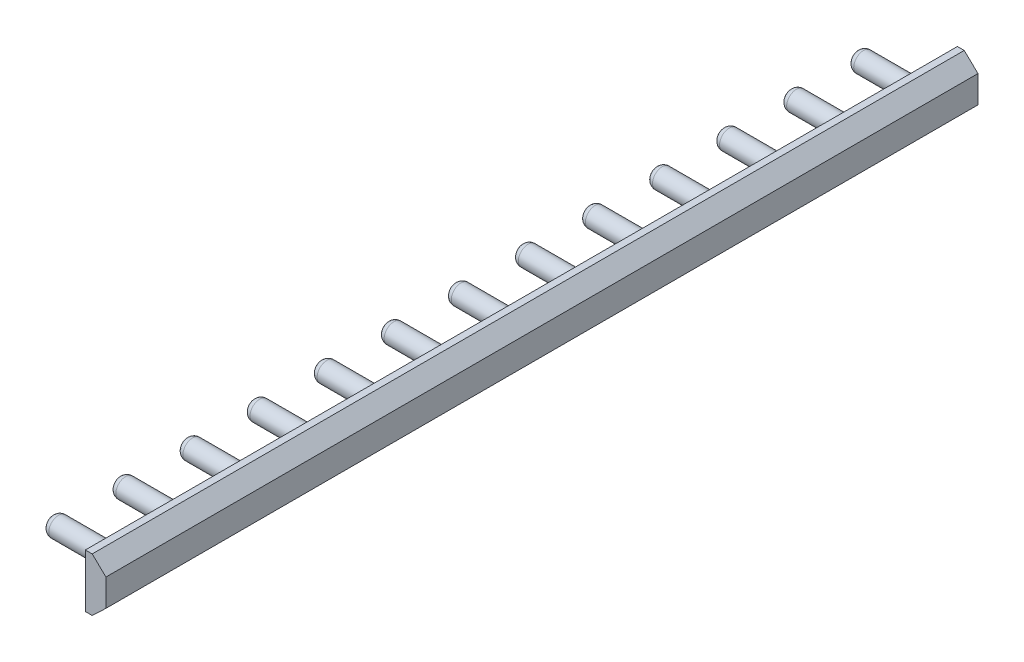
SolidWorks part; units mm, degrees
ref_plane "Front Plane" through (0, 0, 0) normal (0, 0, 1) x (1, 0, 0)
ref_plane "Top Plane" through (0, 0, 0) normal (0, 1, 0) x (1, 0, 0)
ref_plane "Right Plane" through (0, 0, 0) normal (1, 0, 0) x (0, 0, -1)
sketch "Sketch1" plane through (0, 0, 0) normal (0, 0, 1) x (1, 0, 0)
  line B0 (0, 7.95) -> (2.04, 7.95)
  line B1 (6.1524, 4.048) -> (6.1524, -4.048)
  line B2 (2.04, -7.95) -> (0, -7.95)
  line B3 (0, -7.95) -> (0, 7.95)
  line B4 (2.04, 7.95) -> (6.1524, 4.048)
  line B5 (6.1524, -4.048) -> (2.04, -7.95)
sketch_block_instance "Extrusion Profile-1"
sketch_block "Extrusion Profile" parameters "D1"=8.44, "D2"=2.6, "D3"=6, "D4"=16.7, "D6"=5.6686, "D7"=2.0404, "D8"=8.0963, "D9"=15.9, "D5"=2.4157
extrude "Boss-Extrude1" add sketch "Sketch1" along normal blind 260
sketch "Sketch2" plane through (0, 0, 0) normal (-1, 0, 0) x (0, 0, 1)
  circle A0 centre (10, 0) radius 2.9
  circle A1 centre (30, 0) radius 2.9
  circle A2 centre (50, 0) radius 2.9
  circle A3 centre (70, 0) radius 2.9
  circle A4 centre (90, 0) radius 2.9
  circle A5 centre (110, 0) radius 2.9
  circle A6 centre (130, 0) radius 2.9
  circle A7 centre (150, 0) radius 2.9
  circle A8 centre (170, 0) radius 2.9
  circle A9 centre (190, 0) radius 2.9
  circle A10 centre (210, 0) radius 2.9
  circle A11 centre (230, 0) radius 2.9
  circle A12 centre (250, 0) radius 2.9
  dimension "D2" = 5.8
  dimension "D1" = 10
  dimension "D4" = 20
  dimension "D3" = 13
extrude "Boss-Extrude2" add sketch "Sketch2" along normal blind 20
sketch "Sketch3" [suppressed] plane through (0, 0, 0) normal (-1, 0, 0) x (0, 0, 1)
  line L0 (190, 0) -> (210, 0) construction
  line L1 (200, 0) -> (200, 7.95) construction
  line L2 (260, 7.95) -> (0, 7.95) construction
  line L3 (200, 7.95) -> (200, 7)
  line L4 (200, 7) -> (100, 7)
  line L5 (100, 7) -> (100, 7.95)
  line L6 (100, 7.95) -> (200, 7.95)
  line L7 (90, 0) -> (110, 0) construction
  line L8 (100, 0) -> (100, 7) construction
  dimension "D1" = 7
extrude "Cut-Extrude1" [suppressed] cut sketch "Sketch3" against normal through all
chamfer "Chamfer1" [suppressed] distance 3 angle 45
fillet "Fillet1" [suppressed] radius 8
sketch "Sketch4" [suppressed] plane through (0, 0, 0) normal (-1, 0, 0) x (0, 0, 1)
  line L0 (250, 0) -> (230, 0) construction
  line L1 (250, 0) -> (270, 0) construction
  circle A0 centre (270, 0) radius 2.9
  circle A1 centre (250, 0) radius 2.9 construction
  circle A2 centre (290, 0) radius 2.9
  circle A3 centre (310, 0) radius 2.9
  circle A4 centre (330, 0) radius 2.9
  dimension "D2" = 20
  dimension "D1" = 4
extrude "Boss-Extrude3" [suppressed] add sketch "Sketch4" along normal blind 20
sketch "Sketch5" [suppressed] plane through (0, 0, 340) normal (0, 0, 1) x (1, 0, 0)
  line L5 (0, -7.95) -> (0, -20.95)
  line L6 (0, -20.95) -> (6.1524, -20.95)
  line L7 (6.1524, -20.95) -> (6.1524, -4.048)
  line L8 (0, -7.95) -> (2.04, -7.95) construction
  line L9 (0, -7.95) -> (2.04, -7.95)
  line L10 (2.04, -7.95) -> (6.1524, -4.048)
  line L11 (0, 7.95) -> (0, 14.75)
  line L12 (0, 14.75) -> (6.1524, 14.75)
  line L13 (6.1524, 14.75) -> (6.1524, 4.048)
  line L14 (2.04, 7.95) -> (0, 7.95) construction
  line L15 (0, 7.95) -> (2.04, 7.95)
  line L16 (2.04, 7.95) -> (6.1524, 4.048)
  dimension "D1" = 13
  dimension "D2" = 6.8
extrude "Boss-Extrude4" [suppressed] add sketch "Sketch5" against normal up to surface (340 mm away) up to face at (2.7308, 0, 0)
sketch "Sketch7" [suppressed] plane through (0, 0, 340) normal (0, 0, 1) x (1, 0, 0)
  line L0 (6.1524, -20.95) -> (6.1524, 14.75) construction
  line L1 (6.1524, -4.25) -> (0, -4.25)
  line L2 (6.1524, -4.25) -> (6.1524, 3.75)
  line L3 (6.1524, 3.75) -> (0, 3.75)
  line L4 (0, -4.25) -> (0, 3.75)
  line L5 (0, 14.75) -> (0, -20.95) construction
  line L6 (0, -0.25) -> (6.1524, -0.25)
  line L8 (6.1524, 14.75) -> (0, 14.75) construction
  dimension "D1" = 8
  dimension "D2" = 15
extrude "Boss-Extrude5" [suppressed] add sketch "Sketch7" along normal blind 6
ref_plane "Plane1" [suppressed] through (0, 0, 170) normal (0, 0, 1) x (1, 0, 0)
mirror "Mirror1" [suppressed] about plane through (0, 0, 170) normal (0, 0, 1)
sketch "Sketch8" [suppressed] plane through (0, 0, 0) normal (-1, 0, 0) x (0, 0, 1)
  line L0 (0, 7) -> (90, 7)
  line L1 (0, 7.95) -> (0, -7.95) construction
  line L2 (90, 7) -> (90, 7.95)
  line L3 (340, 7.95) -> (0, 7.95) construction
  line L4 (90, 7.95) -> (0, 7.95)
  line L5 (0, 7.95) -> (0, 7)
  circle A0 centre (10, 0) radius 2.9 construction
  dimension "D1" = 7
  dimension "D2" = 90
extrude "Cut-Extrude2" [suppressed] cut sketch "Sketch8" against normal blind 5
fillet "Fillet2" radius 2 13 edges at (-20, -2.9, 10) (-20, -2.9, 250) (-20, -2.9, 230) (-20, -2.9, 210) (-20, -2.9, 190) (-20, -2.9, 170) (-20, -2.9, 150) (-20, -2.9, 130) (-20, -2.9, 110) (-20, -2.9, 90) (-20, -2.9, 70) (-20, -2.9, 50) (-20, -2.9, 30)
fillet "Fillet3" [suppressed] radius 2
